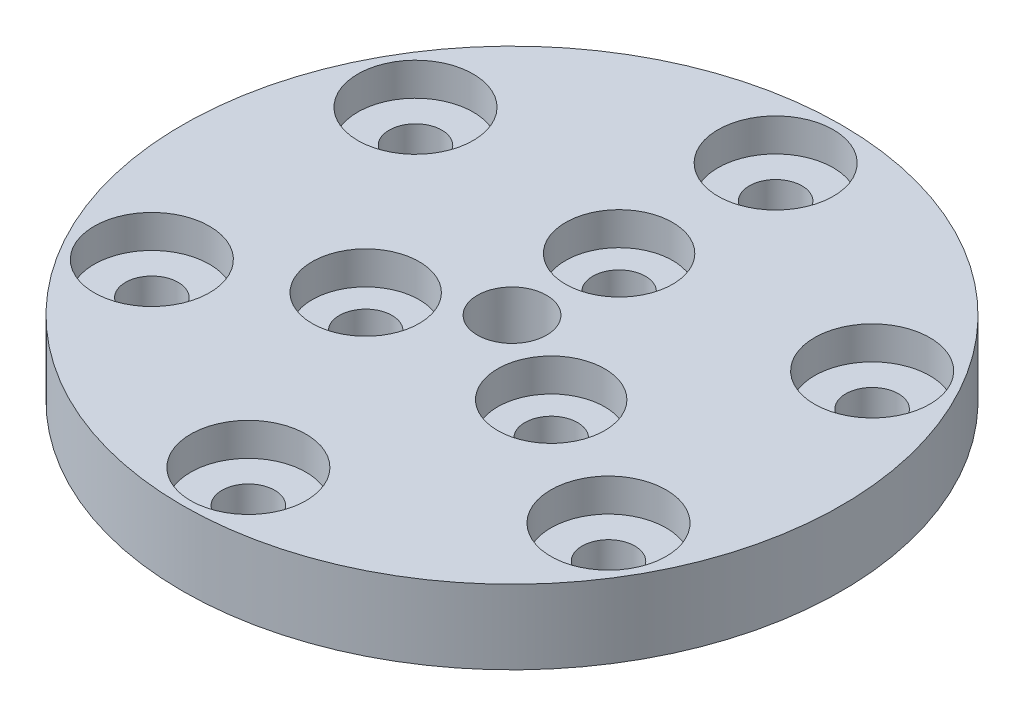
SolidWorks part; units mm, degrees
ref_plane "Front Plane" through (0, 0, 0) normal (0, 0, 1) x (1, 0, 0)
ref_plane "Top Plane" through (0, 0, 0) normal (0, 1, 0) x (1, 0, 0)
ref_plane "Right Plane" through (0, 0, 0) normal (1, 0, 0) x (0, 0, -1)
sketch "Sketch1" plane through (0, 0, 0) normal (0, 1, 0) x (1, 0, 0)
  circle A0 centre (0, 0) radius 20
  circle A1 centre (0, 0) radius 2.1
  dimension "D1" = 4.2
  dimension "D2" = 40
extrude "Boss-Extrude1" add sketch "Sketch1" along normal up to surface (4.5 mm away)
sketch "Sketch2" plane through (0, 0, 0) normal (0, -1, 0) x (1, 0, 0)
  line L0 (0, 0) -> (0, 16) construction
  circle A0 centre (0, 16) radius 1.6
  dimension "D1" = 3.2
  dimension "D2" = 16
extrude "Cut-Extrude1" cut sketch "Sketch2" against normal through all
sketch "Sketch5" plane through (0, 4.5, 0) normal (0, 1, 0) x (1, 0, 0)
  circle A4 centre (0, -16) radius 3.5
  circle A5 centre (0, -16) radius 1.6 construction
  circle A6 centre (0, -16) radius 1.6 construction
  dimension "D1" = 7
extrude "Cut-Extrude4" cut sketch "Sketch5" against normal blind 2
pattern_circular "CirPattern1" count 6 over 360 about axis through (0, 61.0685, 0) along (0, -1, 0) of "Cut-Extrude1", "Cut-Extrude4"
sketch "Sketch3" plane through (0, 4.5, 0) normal (0, 1, 0) x (1, 0, 0)
  line L0 (0, 0) -> (0, 6.5) construction
  circle A0 centre (0, 6.5) radius 1.6
  dimension "D1" = 3.2
  dimension "D2" = 6.5
extrude "Cut-Extrude2" cut sketch "Sketch3" against normal through all
sketch "Sketch4" plane through (0, 4.5, 0) normal (0, 1, 0) x (1, 0, 0)
  circle A0 centre (0, 6.5) radius 3.25
  dimension "D1" = 6.5
extrude "Cut-Extrude3" cut sketch "Sketch4" against normal blind 2
pattern_circular "CirPattern2" count 3 over 360 about axis through (0, 61.0685, 0) along (0, -1, 0) of "Cut-Extrude2", "Cut-Extrude3"
